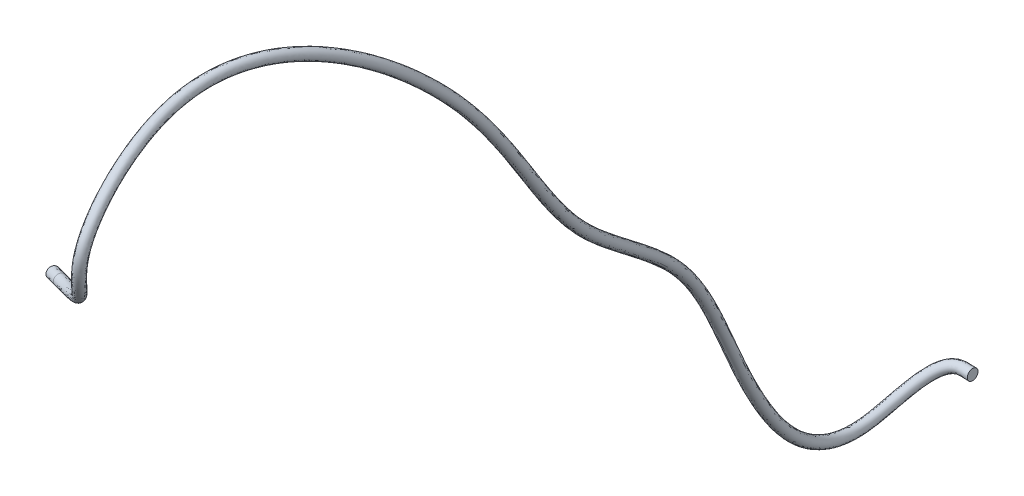
SolidWorks part; units mm, degrees
material "Natural Rubber"
ref_plane "Front Plane" through (0, 0, 0) normal (1, 0, 0) x (0, 1, 0)
ref_plane "Top Plane" through (0, 0, 0) normal (0, 0, 1) x (0, 1, 0)
ref_plane "Right Plane" through (0, 0, 0) normal (0, 1, 0) x (-1, 0, 0)
sketch3d "3DSketch1"
  line L0 (-155.0528, 317.5703, 594.6437) -> (-146.5956, 318.5057, 597.5763) construction
  line L1 (-155.0528, 317.5703, 594.6437) -> (-146.5956, 318.5057, 597.5763)
  line L5 (-63.62, 0, 0) -> (-72.62, 0, 0) construction
  spline S0 degree 3 poles (-146.5956, 318.5057, 597.5763) (-112.7468, 322.2493, 609.3137) (-86.5169, 381.8803, 660.6272) (-125.3948, 463.063, 513.943) (-50.6632, 385.6809, 373.2698) (-61.6908, 243.6157, 313.6685) (-71.8568, 168.5853, 189.9183) (-85.5918, 54.3064, 155.8463) (-89.1075, -38.8823, 79.3154) (-89.8311, 1.1506, -2.347) (-67.0907, 0, 0) (-63.62, 0, 0) knots 0 0 0 0 0.083846 0.186318 0.385687 0.548528 0.657307 0.822755 0.926818 0.990475 1 1 1 1
  point P10 (-104.7592, 422.557, 576.3305)
  point P23 (-52.8604, 89.8604, -16.6865)
  point P24 (-108.6047, 110.0277, -18.2769)
sweep "Sweep1" add path "3DSketch1" circular profile diameter 8 parameters "D3"=8
